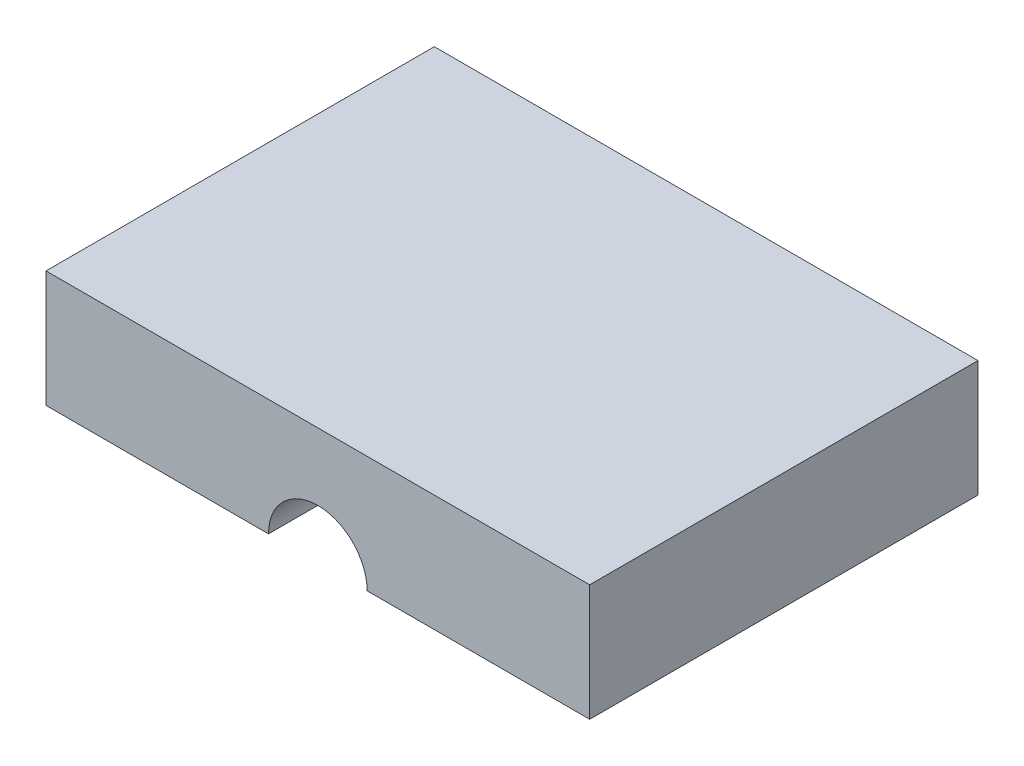
SolidWorks part; units mm, degrees
ref_plane "Front Plane" through (0, 0, 0) normal (0, 0, 1) x (1, 0, 0)
ref_plane "Top Plane" through (0, 0, 0) normal (0, 1, 0) x (1, 0, 0)
ref_plane "Right Plane" through (0, 0, 0) normal (1, 0, 0) x (0, 0, -1)
sketch "Sketch1" plane through (0, 0, 0) normal (0, 0, 1) x (1, 0, 0)
  line L1 (-35, 15) -> (35, 15)
  line L2 (-35, 15) -> (-35, 0)
  line L4 (35, 15) -> (35, 0)
  line L8 (-35, 0) -> (35, 0)
  arc A0 (6.35, 0) -> (-6.35, 0) centre (0, 0) ccw
  point P0 (0, 0)
  dimension "D1" = 12.7
  dimension "D2" = 15
  dimension "D3" = 70
extrude "Boss-Extrude1" add sketch "Sketch1" along normal blind 50 contours A0 L8 L4 L1 L2 region at (0, 7.8085, 0)
